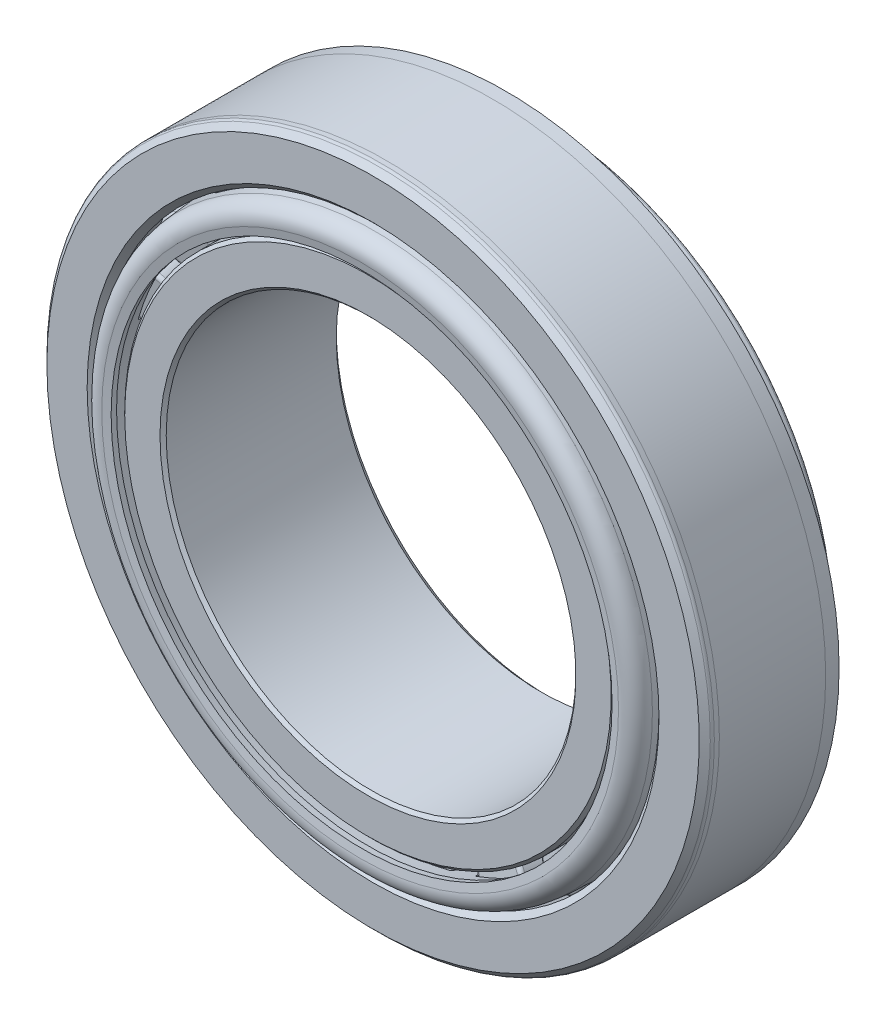
SolidWorks part; units mm, degrees
ref_plane "Front Plane" through (0, 0, 0) normal (0, 0, 1) x (1, 0, 0)
ref_plane "Top Plane" through (0, 0, 0) normal (0, 1, 0) x (1, 0, 0)
ref_plane "Right Plane" through (0, 0, 0) normal (1, 0, 0) x (0, 0, -1)
sketch "Sketch1" plane through (0, 0, 0) normal (1, 0, 0) x (0, 0, -1)
  line L0 (-8.255, 41.275) -> (-8.255, 34.62)
  line L1 (-8.255, 34.62) -> (8.255, 37.98)
  line L2 (8.255, 37.98) -> (8.255, 41.275)
  line L3 (8.255, 41.275) -> (-8.255, 41.275)
  line L4 (0, 0) -> (10110.1541, 0) construction
  line L5 (0.1013, 36.3206) -> (7.493, 0) construction
  line L6 (13.335, 32.945) -> (13.335, 25.4)
  line L7 (13.335, 25.4) -> (-8.89, 25.4)
  line L8 (-8.89, 25.4) -> (-8.89, 30.545)
  line L9 (-8.89, 30.545) -> (-6.2619, 30.545)
  line L10 (13.335, 32.945) -> (7.9486, 32.945)
  line L12 (13.335, 41.275) -> (-9.906, 41.275) construction
  line L14 (-9.906, 32.2972) -> (12.4201, 36.4308)
  line L15 (12.4201, 36.4308) -> (12.573, 35.6049)
  line L16 (12.573, 35.6049) -> (-8.9271, 31.6241)
  line L17 (-8.9271, 31.6241) -> (-8.8506, 31.2111)
  line L18 (-7.0614, 34.8629) -> (7.0614, 37.7371) construction
  line L19 (-9.906, 32.2972) -> (-9.6766, 31.0582)
  line L20 (-9.6766, 31.0582) -> (-8.8506, 31.2111)
  line L21 (7.0614, 37.7371) -> (8.2812, 31.1491)
  line L22 (8.2812, 31.1491) -> (-5.9345, 28.7764)
  line L23 (-5.9345, 28.7764) -> (-7.0614, 34.8629)
  line L25 (-6.4979, 31.8196) -> (7.6713, 34.4431) construction
  line L27 (0, 36.3) -> (0.5867, 33.1314) construction
  line L28 (0.5867, 33.1314) -> (1.1734, 29.9627) construction
  line L29 (-9.906, 41.275) -> (-9.906, 32.2972) construction
  point P7 (0, 41.275)
  point P44 (7.6258, 34.6889)
  dimension "Width" = 16.51
  dimension "Inner Ring Width" = 22.225
  dimension "Effective Center" = 5.842
  dimension "Width A" = 21.59
  dimension "Cone Thick" = 0.84
  dimension "D17" = 0.42
  dimension "Roller S Diameter" = 6.19
  dimension "Roller L Diameter" = 6.7
  dimension "Roller Length" = 14.41
  dimension "D2" = 0.25
  dimension "Back Cone Dim" = 0.762
  dimension "Diameter B" = 69.24
  dimension "Diameter C" = 61.09
  dimension "Diameter F" = 75.96
  dimension "Diameter E" = 65.89
  dimension "D3" = 23.241
  dimension "ID" = 50.8
  dimension "OD" = 82.55
  dimension "Cage Width" = 23.241
sketch "Sketch0" plane through (0, 0, 0) normal (0, 0, 1) x (1, 0, 0)
  circle A0 centre (0, 0) radius 25.4
  circle A1 centre (0, 0) radius 41.275
  dimension "D1" = 82.55
  dimension "D2" = 50.8
sketch "Sketch2" plane through (0, 0, 0) normal (1, 0, 0) x (0, 0, -1)
  line L0 (-8.255, 41.275) -> (-8.255, 34.62)
  line L1 (-8.255, 34.62) -> (8.255, 37.98)
  line L2 (8.255, 37.98) -> (8.255, 41.275)
  line L3 (8.255, 41.275) -> (-8.255, 41.275)
revolve "Revolve1" add sketch "Sketch2" angle 360 about L4
sketch "Sketch3" plane through (0, 0, 0) normal (1, 0, 0) x (0, 0, -1)
  line L0 (-8.89, 30.545) -> (-8.89, 25.4)
  line L1 (-8.89, 25.4) -> (13.335, 25.4)
  line L2 (13.335, 25.4) -> (13.335, 32.945)
  line L3 (13.335, 32.945) -> (7.9486, 32.945)
  line L4 (7.9486, 32.945) -> (8.2812, 31.1491)
  line L5 (8.2812, 31.1491) -> (-5.9345, 28.7764)
  line L6 (-5.9345, 28.7764) -> (-6.2619, 30.545)
  line L7 (-6.2619, 30.545) -> (-8.89, 30.545)
revolve "Revolve2" add sketch "Sketch3" angle 360 about L4
sketch "Sketch4" plane through (0, 0, 0) normal (1, 0, 0) x (0, 0, -1)
  line L0 (12.573, 35.6049) -> (12.4201, 36.4308)
  line L1 (12.4201, 36.4308) -> (-10.2623, 34.2215)
  line L2 (-10.2623, 34.2215) -> (-9.6766, 31.0582)
  line L3 (-9.6766, 31.0582) -> (-8.8506, 31.2111)
  line L4 (-8.8506, 31.2111) -> (-8.9271, 31.6241)
  line L5 (-8.9271, 31.6241) -> (12.573, 35.6049)
  line L6 (-7.0614, 34.8629) -> (-9.906, 32.2972) construction
  line L7 (-8.4837, 33.58) -> (-7.0614, 34.8629) construction
  point P14 (-7.7725, 34.2215)
revolve "Revolve3" add sketch "Sketch4" angle 360 about L4
sketch "Sketch6" plane through (0, 0, 0) normal (1, 0, 0) x (0, 0, -1)
  line L0 (8.2812, 31.1491) -> (7.6713, 34.4431)
  line L1 (7.6713, 34.4431) -> (-6.4979, 31.8196)
  line L3 (-6.4979, 31.8196) -> (-5.9345, 28.7764)
  line L4 (-5.9345, 28.7764) -> (8.2812, 31.1491)
  line L5 (-6.4979, 31.8196) -> (7.6713, 34.4431) construction
  line L6 (-5.9345, 28.7764) -> (-7.0614, 34.8629) construction
revolve "Revolve4" add sketch "Sketch6" angle 360 about L25
sketch "Sketch8" plane through (0, 2.5149, -13.5828) normal (0, 0.1821, -0.9833) x (-1, 0, 0)
  line L0 (0, 29.1209) -> (0, 32.4709) construction
  circle A0 centre (0, 32.4709) radius 1.675
  point P3 (0, 30.7959)
extrude "Cut-Extrude1" cut sketch "Sketch8" against normal blind 0.635
fillet "Fillet7" radius 0.9525 1 edges at (0, 35.9745, -6.7419)
chamfer "Chamfer4" distance 0.4187 angle 45 1 edges at (0, 31.1491, -8.2812)
fillet "Fillet8" radius 0.4643 1 edges at (0, 28.7764, 5.9345)
pattern_circular "CirPattern1" count 21 over 360 about axis through (0, 0, 0) along (0, 0, 1) of "Revolve4"
fillet "Fillet9" radius 2.0375 1 edges at (34.2215, 0, 10.2623)
fillet "Fillet10" radius 0.273 2 edges at (36.4308, 0, -12.4201) (35.6049, 0, -12.573)
sketch "Sketch9" plane through (0, 0, 0) normal (1, 0, 0) x (0, 0, -1)
  line L0 (-6.4979, 31.8196) -> (7.6713, 34.4431)
  line L1 (7.6713, 34.4431) -> (8.3234, 30.9208)
  line L2 (8.3234, 30.9208) -> (-5.8922, 28.5481)
  line L3 (-5.8922, 28.5481) -> (-6.4979, 31.8196)
  line L4 (-5.9345, 28.7764) -> (8.2812, 31.1491) construction
  dimension "D1" = 0.2321
revolve "Cut-Revolve2" cut sketch "Sketch9" angle 360 about L0
fillet "Fillet11" radius 0.3095 4 edges at (-2.9381, 33.3548, 6.7822) (2.9381, 33.3548, 6.7822) (3.5065, 35.163, -7.538) (-3.5065, 35.163, -7.538)
pattern_circular "CirPattern2" count 21 over 360 about axis through (0, 0, 0) along (0, 0, 1) of "Cut-Revolve2", "Fillet11"
chamfer "Chamfer1" distance 0.8319 angle 45 2 edges at (41.275, 0, 8.255) (34.62, 0, 8.255)
ref_plane "Plane1" through (0, 0, 6.5913) normal (0, 0, 1) x (1, 0, 0)
ref_plane "Plane2" through (0, 0, -6.5913) normal (0, 0, -1) x (-1, 0, 0)
split line "Split Line1"
split line "Split Line2"
fillet "Fillet6" radius 0.4991 1 edges at (-41.275, 0, 7.4231)
chamfer "Chamfer2" distance 0.3859 angle 45 2 edges at (30.545, 0, 8.89) (25.4, 0, 8.89)
chamfer "Chamfer3" distance 0.7545 angle 45 2 edges at (25.4, 0, -13.335) (32.945, 0, -13.335)
sketch "Sketch7" plane through (0, 0, 0) normal (1, 0, 0) x (0, 0, -1)
  line L0 (13.335, 32.945) -> (13.335, 25.4) construction
  line L1 (-8.89, 30.545) -> (-6.2619, 30.545) construction
  line L2 (-8.89, 25.4) -> (-8.89, 30.545) construction
  line L3 (13.335, 25.4) -> (-8.89, 25.4) construction
  line L4 (13.335, 32.945) -> (7.9486, 32.945) construction
  line L5 (8.2812, 31.1491) -> (-5.9345, 28.7764) construction
  line L6 (7.0614, 37.7371) -> (8.2812, 31.1491) construction
  line L7 (-8.255, 34.62) -> (8.255, 37.98) construction
  line L8 (-5.9345, 28.7764) -> (-7.0614, 34.8629) construction
  line L9 (13.335, 32.945) -> (13.335, 25.4)
  line L10 (-8.89, 30.545) -> (-6.2619, 30.545)
  line L11 (-8.89, 25.4) -> (-8.89, 30.545)
  line L12 (13.335, 25.4) -> (-8.89, 25.4)
  line L13 (13.335, 32.945) -> (7.9486, 32.945)
  line L14 (8.2812, 31.1491) -> (-5.9345, 28.7764)
  line L15 (7.0614, 37.7371) -> (8.2812, 31.1491)
  line L16 (-7.0614, 34.8629) -> (7.0614, 37.7371)
  line L17 (-5.9345, 28.7764) -> (-7.0614, 34.8629)
  line L18 (0, 0) -> (13.335, 0) construction
  line L21 (-5.9345, -28.7764) -> (-7.0614, -34.8629)
  line L22 (-7.0614, -34.8629) -> (7.0614, -37.7371)
  line L23 (7.0614, -37.7371) -> (8.2812, -31.1491)
  line L24 (8.2812, -31.1491) -> (-5.9345, -28.7764)
  line L25 (13.335, -32.945) -> (7.9486, -32.945)
  line L26 (13.335, -25.4) -> (-8.89, -25.4)
  line L27 (-8.89, -25.4) -> (-8.89, -30.545)
  line L28 (-8.89, -30.545) -> (-6.2619, -30.545)
  line L29 (13.335, -32.945) -> (13.335, -25.4)
equation "\"D17@Sketch1\" = \"Cone Thick@Sketch1\" / 2"
equation "\"D1@Chamfer1\"=(\"OD@Sketch1\"-\"Diameter B@Sketch1\")*0.5*0.125"
equation "\"D1@Plane1\"=(\"OD@Sketch1\"-\"Diameter B@Sketch1\")*0.5*0.25"
equation "\"D1@Plane2\"=(\"OD@Sketch1\"-\"Diameter B@Sketch1\")*0.5*0.25"
equation "\"D1@Fillet6\"=(\"OD@Sketch1\"-\"Diameter B@Sketch1\")*0.5*0.075"
equation "\"D1@Chamfer2\"=(\"Diameter C@Sketch1\"-\"ID@Sketch1\")*0.5*0.075"
equation "\"D1@Chamfer3\"=(\"Diameter E@Sketch1\"-\"ID@Sketch1\")*0.5*0.1"
equation "\"D1@Chamfer4\"=\"Roller L Diameter@Sketch1\"*0.0625"
equation "\"D1@Fillet8\"=\"Roller S Diameter@Sketch1\"*0.075"
equation "\"D1@Fillet9\"=(\"Diameter B@Sketch1\"-\"Diameter C@Sketch1\")*0.5*0.5"
equation "\"D1@Fillet10\"=\"Cone Thick@Sketch1\"*0.325"
equation "\"D1@Sketch9\"=\"Roller S Diameter@Sketch1\"*0.0375"
equation "\"D1@Fillet11\"=\"Roller S Diameter@Sketch1\"*0.05"
equation "\"D1@CirPattern2\"=\"Number of Rollers@CirPattern1\""
